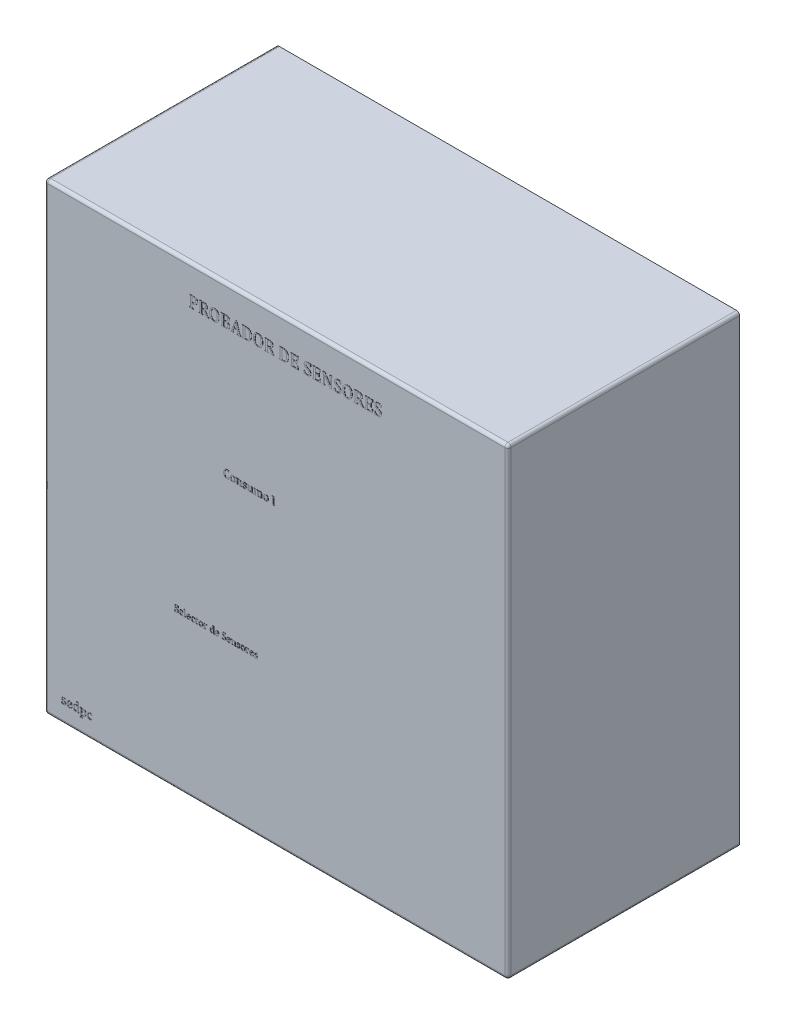
SolidWorks part; units mm, degrees
ref_plane "Alzado" through (0, 0, 0) normal (0, 0, 1) x (1, 0, 0)
ref_plane "Planta" through (0, 0, 0) normal (0, 1, 0) x (1, 0, 0)
ref_plane "Vista lateral" through (0, 0, 0) normal (1, 0, 0) x (0, 0, -1)
sketch "Croquis1" plane through (0, 0, 0) normal (0, 0, 1) x (1, 0, 0)
  line L1 (0, 0) -> (300, 0)
  line L2 (0, 0) -> (0, 300)
  line L3 (0, 300) -> (300, 300)
  line L4 (300, 0) -> (300, 300)
  dimension "D1" = 300
  dimension "D2" = 300
extrude "Saliente-Extruir1" add sketch "Croquis1" along normal blind 150
sketch "Croquis2" plane through (0, 0, 150) normal (0, 0, 1) x (1, 0, 0)
  line L0 (90.6932, 274.7092) -> (251.8517, 274.7092) construction
  text T0 " PROBADOR DE SENSORES" font "Cambria" height in points 27
extrude "Saliente-Extruir2" add sketch "Croquis2" along normal blind 0.1
sketch "Croquis4" plane through (0, 0, 150) normal (0, 0, 1) x (1, 0, 0)
  line L0 (115.6547, 190.7877) -> (173.112, 190.7877) construction
  text T0 "Consumo I" font "Cambria" height in points 18
extrude "Saliente-Extruir3" add sketch "Croquis4" along normal blind 0.1
sketch "Croquis5" plane through (0, 0, 150) normal (0, 0, 1) x (1, 0, 0)
  line L0 (83.8331, 99.3106) -> (156.8513, 99.3106) construction
  text T0 "Selector de Sensores\r\n" font "Cambria" height in points 15
  point P3 (156.8513, 100.0408)
  point P4 (83.8331, 99.3106)
extrude "Saliente-Extruir4" add sketch "Croquis5" along normal blind 0.1
fillet "Redondeo1" radius 2 8 edges at (300, 0, 75) (150, 0, 150) (0, 0, 75) (300, 150, 150) (300, 300, 75) (150, 300, 150) (0, 150, 150) (0, 300, 75)
sketch "Croquis7" plane through (0, 0, 150) normal (0, 0, 1) x (1, 0, 0)
  line L0 (10.5568, 11.1632) -> (37.4251, 11.1632) construction
  text T0 "sedpc" font "Cambria" height in points 20
extrude "Saliente-Extruir5" add sketch "Croquis7" along normal blind 0.1
sketch "Croquis8" plane through (0, 0, 0) normal (0, -1, 0) x (1, 0, 0)
  line L0 (2, 150) -> (298, 150) construction
  line L1 (196, 120) -> (250, 120)
  line L2 (196, 120) -> (196, 86)
  line L3 (196, 86) -> (250, 86)
  line L4 (250, 120) -> (250, 86)
  line L5 (300, 148) -> (300, 0) construction
  line L6 (223, 120) -> (223, 86) construction
  line L7 (250, 103) -> (196, 103) construction
  circle A0 centre (257.25, 118.75) radius 1.5
  circle A1 centre (188.75, 118.75) radius 1.5
  circle A2 centre (257.25, 87.25) radius 1.5
  circle A3 centre (188.75, 87.25) radius 1.5
  dimension "D5" = 3
  dimension "D6" = 3
  dimension "D1" = 34
  dimension "D2" = 54
  dimension "D3" = 30
  dimension "D4" = 50
  dimension "D7" = 15.75
  dimension "D8" = 15.75
  dimension "D9" = 34.25
  dimension "D10" = 34.25
extrude "Cortar-Extruir1" cut sketch "Croquis8" against normal blind 10
